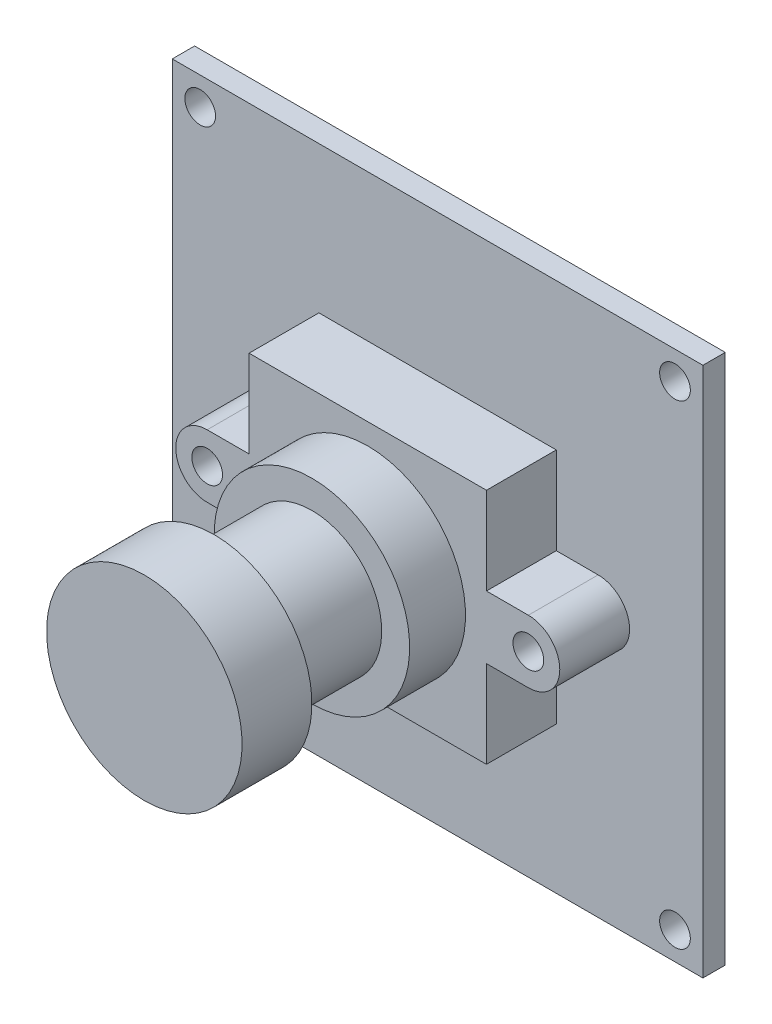
SolidWorks part; units mm, degrees
ref_plane "前视基准面" through (0, 0, 0) normal (0, 0, 1) x (1, 0, 0)
ref_plane "上视基准面" through (0, 0, 0) normal (0, 1, 0) x (1, 0, 0)
ref_plane "右视基准面" through (0, 0, 0) normal (1, 0, 0) x (0, 0, -1)
other "Configuration Table"
sketch "草图1" plane through (0, 0, 0) normal (0, 0, 1) x (1, 0, 0)
  line L0 (-17, 17) -> (17, 17) construction
  line L1 (-19, -19) -> (19, -19)
  line L2 (-19, -19) -> (-19, 19)
  line L3 (-19, 19) -> (19, 19)
  line L4 (19, -19) -> (19, 19)
  line L5 (-19, -19) -> (19, 19) construction
  line L6 (-19, 19) -> (19, -19) construction
  line L7 (-17, 17) -> (-17, -17) construction
  line L8 (-11.5, 0) -> (11.5, 0) construction
  line L9 (-8.5, -8.5) -> (8.5, -8.5)
  line L10 (-8.5, -8.5) -> (-8.5, 8.5)
  line L11 (-8.5, 8.5) -> (8.5, 8.5)
  line L12 (8.5, -8.5) -> (8.5, 8.5)
  line L13 (-8.5, -8.5) -> (8.5, 8.5) construction
  line L14 (-8.5, 8.5) -> (8.5, -8.5) construction
  line L15 (-11.5, 2.25) -> (11.5, 2.25)
  line L16 (-11.5, -2.25) -> (11.5, -2.25)
  circle A0 centre (-17, 17) radius 1.1
  circle A1 centre (17, 17) radius 1.1
  circle A2 centre (17, -17) radius 1.1
  circle A3 centre (-17, -17) radius 1.1
  arc A4 (-11.5, 2.25) -> (-11.5, -2.25) centre (-11.5, 0) ccw
  arc A5 (11.5, -2.25) -> (11.5, 2.25) centre (11.5, 0) ccw
  circle A6 centre (11.5, 0) radius 1.1
  circle A7 centre (-11.5, 0) radius 1.1
  point P0 (0, 0)
  point P19 (0, 0)
  point P24 (0, 0)
  dimension "D2" = 2.2
  dimension "D7" = 34
  dimension "D12" = 2.2
  dimension "D1" = 38
  dimension "D5" = 2
  dimension "D6" = 2
  dimension "D8" = 34
  dimension "D9" = 17
  dimension "D10" = 23
  dimension "D11" = 4.5
  dimension "D3" = 2
  dimension "D4" = 2
extrude "凸台-拉伸2" add sketch "草图1" against normal blind 1.6 contours L3 L4 L1 L2 | A0 | A1 | A2 | A3
extrude "凸台-拉伸3" add sketch "草图1<4>" along normal blind 5 contours L11 L12 L9 L10 | L15 A5 L16 A4 | A6 | A7
sketch "草图1<4>" plane through (0, 0, 0) normal (0, 0, 1) x (1, 0, 0) same geometry as "草图1"
sketch "草图3" plane through (0, 0, 0) normal (1, 0, 0) x (0, 0, -1)
  line L0 (-5, 2.25) -> (-5, -2.25) construction
  line L1 (-5, 0) -> (-36.3847, 0) construction
  line L2 (-5, 0) -> (-9, 0)
  line L3 (-5, 0) -> (-5, 7)
  line L4 (-5, 7) -> (-9, 7)
  line L5 (-9, 5) -> (-9, 7)
  line L6 (-9, 0) -> (-16, 0)
  line L8 (-9, 5) -> (-16, 5)
  line L10 (-16, 0) -> (-21, 0)
  line L11 (-16, 5) -> (-16, 7)
  line L12 (-16, 7) -> (-21, 7)
  line L13 (-21, 0) -> (-21, 7)
  point P0 (-5, 0)
  dimension "D1" = 7
  dimension "D2" = 5
  dimension "D3" = 7
  dimension "D4" = 7
  dimension "D5" = 4
  dimension "D6" = 5
revolve "旋转3" add sketch "草图3" angle 360 about L1
sketch "草图4" plane through (0, 0, -1.6) normal (0, 0, -1) x (-1, 0, 0)
  line L0 (19, -19) -> (-19, -19) construction
  line L1 (-12, -13.8) -> (-6, -13.8)
  line L2 (-12, -13.8) -> (-12, -16.8)
  line L3 (-12, -16.8) -> (-6, -16.8)
  line L4 (-6, -13.8) -> (-6, -16.8)
  line L5 (-2.5, -13.8) -> (6.5, -13.8)
  line L6 (-2.5, -13.8) -> (-2.5, -16.8)
  line L7 (-2.5, -16.8) -> (6.5, -16.8)
  line L8 (6.5, -13.8) -> (6.5, -16.8)
  line L9 (-19, -19) -> (-19, 19) construction
  circle A0 centre (17, -17) radius 1.1 construction
  circle A1 centre (17, -17) radius 1.1 construction
  point P11 (-12, -15.3)
  dimension "D1" = 3
  dimension "D2" = 6
  dimension "D3" = 9
  dimension "D4" = 2.2
  dimension "D5" = 7
  dimension "D6" = 10.5
extrude "凸台-拉伸4" add sketch "草图4" along normal blind 8.3 from surface starting at plane "前视基准面"
